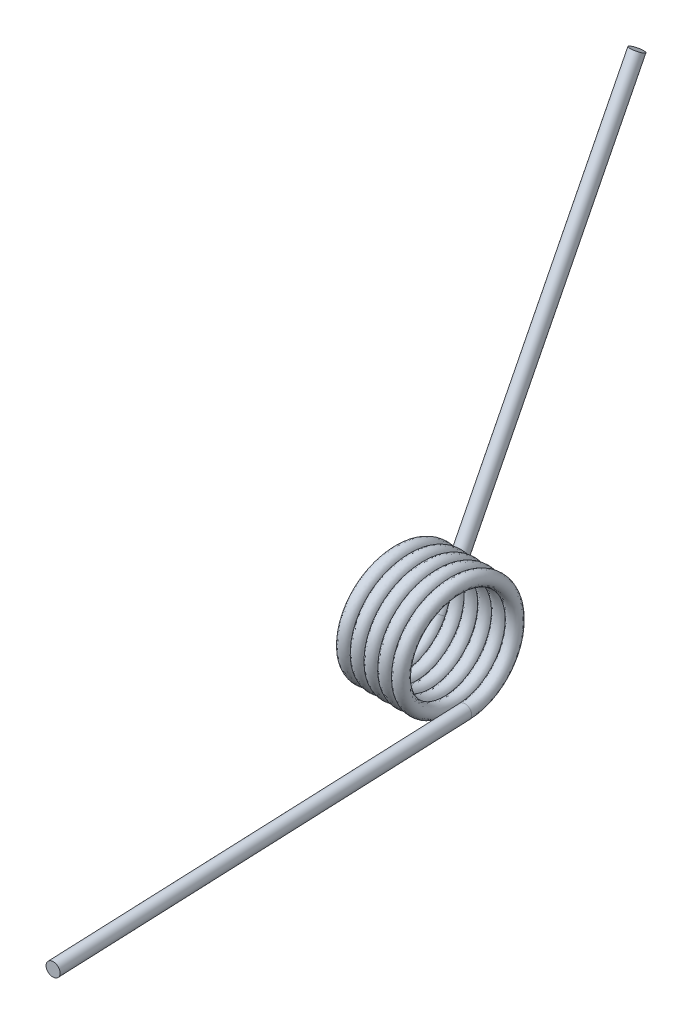
SolidWorks part; units mm, degrees
note: '?' marks a value the reader was unsure of.
material "Plain Carbon Steel"
ref_plane "Front" through (0, 0, 0) normal (0, 0, 1) x (1, 0, 0)
ref_plane "Top" through (0, 0, 0) normal (0, 1, 0) x (1, 0, 0)
ref_plane "Right" through (0, 0, 0) normal (1, 0, 0) x (0, 0, -1)
sketch "Sketch1" plane through (0, 0, 0) normal (1, 0, 0) x (0, 0, -1)
  line L0 (0, -5.5118) -> (0, -7.112) construction
  line L1 (6.1592, -3.556) -> (31.5592, 40.4381) construction
  line L2 (0, -7.112) -> (-50.8, -7.112) construction
  line L3 (0, 0) -> (7.112, 0) construction
  line L4 (0, 0) -> (6.1592, -3.556) construction
  line L5 (-50.8, -7.112) -> (-50.8, -5.5118) construction
  line L6 (-50.8, -5.5118) -> (0, -5.5118) construction
  line L7 (31.5592, 40.4381) -> (30.1734, 41.2382) construction
  line L8 (30.1734, 41.2382) -> (4.7734, -2.7559) construction
  circle A0 centre (0, 0) radius 7.112 construction
  circle A1 centre (0, 0) radius 4.3561 construction
  circle A2 centre (0, 0) radius 6.3119 construction
  point P7 (0, -6.3119)
  point P10 (0, 7.112)
  dimension "OD" = 14.224
  dimension "For Shaft Diameter" = 8.7122
  dimension "Wire Diameter" = 1.6002
  dimension "Leg Length" = 50.8
  dimension "Deflection Angle" = 120
sketch "Sketch2" plane through (0, 0, 0) normal (1, 0, 0) x (0, 0, -1)
  circle A0 centre (0, 0) radius 6.3119 construction
  circle A2 centre (0, 0) radius 6.3119
curve "Helix/Spiral1" pitch 1.6256 height 8.3989 turns 5.1667
ref_plane "Plane1" through (0, -6.3119, 0) normal (-0.041, 0, -0.9992) x (0.9989, -0.0232, -0.0409)
sketch "Sketch3" plane through (0, -6.3119, 0) normal (-0.041, 0, -0.9992) x (0.9989, -0.0232, -0.0409)
  circle A0 centre (0, 0) radius 0.8001
  dimension "D1" = 1.6002
sweep "Sweep1" add profiles "Sketch3" path "Helix/Spiral1"
sketch "Sketch4" plane through (0, 0, 0) normal (0.041, 0, 0.9992) x (-0.9989, 0.0232, 0.0409)
  circle A1 centre (-0.1467, 6.3102) radius 0.8001
  circle A2 centre (-0.1467, 6.3102) radius 0.8001
  dimension "D1" = 0
extrude "Extrude1" add sketch "Sketch4" along normal blind 50.8
sketch "Sketch5" plane through (-0.0141, 0.2976, -0.1718) normal (-0.041, 0.8653, -0.4996) x (0.9992, 0.0355, -0.0204)
  circle A1 centre (-8.3921, 6.3116) radius 0.8001
  circle A2 centre (-8.3921, 6.3116) radius 0.8001
  dimension "D1" = 0
extrude "Extrude2" add sketch "Sketch5" along normal blind 50.8
sketch "Sketch6" plane through (0, 0, 0) normal (1, 0, 0) x (0, 0, -1)
  circle A2 centre (0, 0) radius 5.5118 construction
ref_axis "Axis1" through (3.5879, 0, 0) along (-1, 0, 0)?
equation "\"D4@Helix/Spiral1\" = \"Wire Diameter@Sketch1\" + .001"
equation "\"D1@Sketch3\"=\"Wire Diameter@Sketch1\""
equation "\"D1@Extrude2\"=\"Leg Length@Sketch1\""
equation "\"Leg Length@Extrude1\"=\"Leg Length@Sketch1\""
